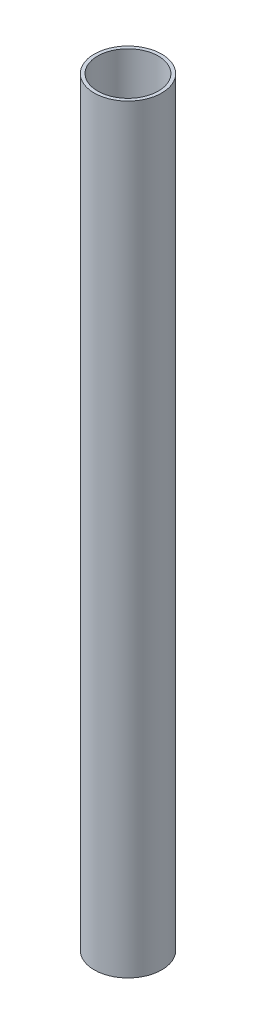
SolidWorks part; units mm, degrees
material "Thornel VCB-20 Carbon Cloth"
ref_plane "Front Plane" through (0, 0, 0) normal (0, 0, 1) x (1, 0, 0)
ref_plane "Top Plane" through (0, 0, 0) normal (0, 1, 0) x (1, 0, 0)
ref_plane "Right Plane" through (0, 0, 0) normal (1, 0, 0) x (0, 0, -1)
sketch "Sketch1" plane through (0, 0, 0) normal (0, 1, 0) x (1, 0, 0)
  circle A0 centre (0, 0) radius 10
  circle A1 centre (0, 0) radius 9
  dimension "D1" = 18
  dimension "D2" = 20
extrude "Boss-Extrude1" add sketch "Sketch1" along normal blind 225
